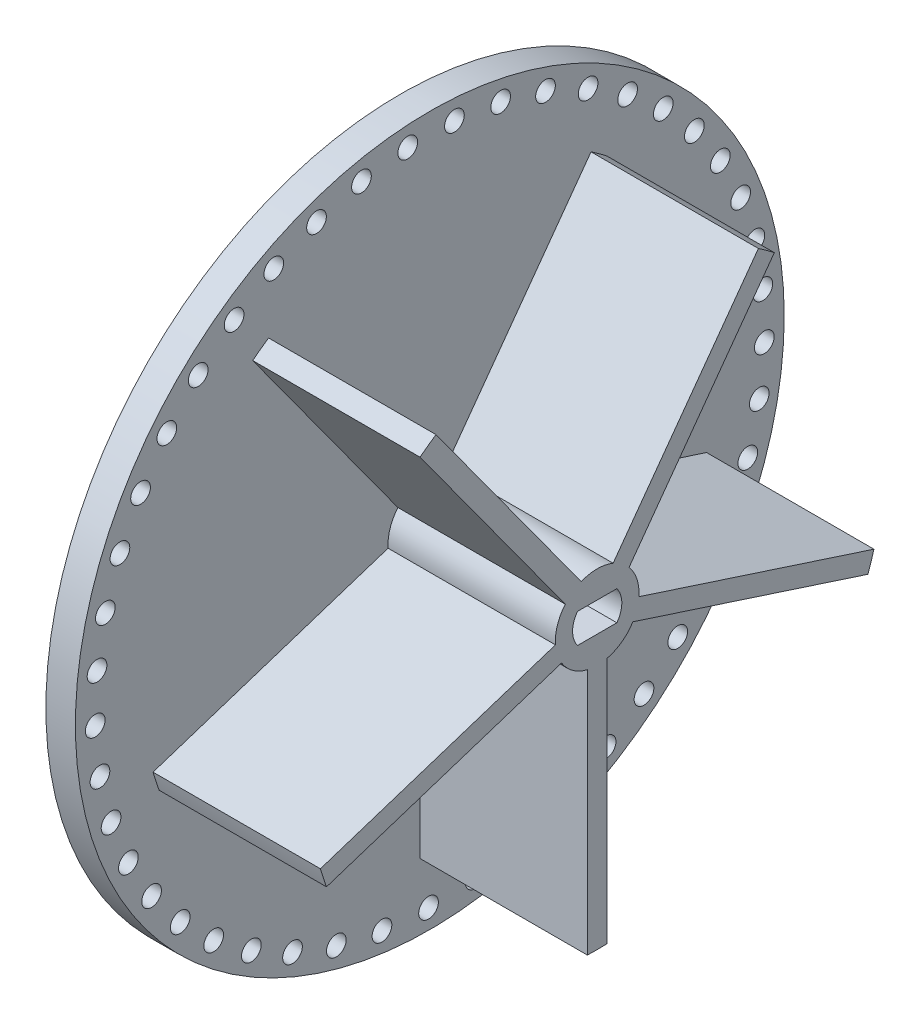
SolidWorks part; units mm, degrees
material "ABS"
ref_plane "Front Plane" through (0, 0, 0) normal (0, 0, 1) x (1, 0, 0)
ref_plane "Top Plane" through (0, 0, 0) normal (0, 1, 0) x (1, 0, 0)
ref_plane "Right Plane" through (0, 0, 0) normal (1, 0, 0) x (0, 0, -1)
sketch "Sketch1" plane through (0, 0, 0) normal (1, 0, 0) x (0, 0, -1)
  line L0 (0, 0) -> (20.089, 27.4305) construction
  line L1 (-2, 1.5) -> (2, 1.5)
  line L3 (-2, -1.5) -> (2, -1.5)
  line L5 (-2, 1.5) -> (2, -1.5) construction
  line L6 (-2, -1.5) -> (2, 1.5) construction
  circle A0 centre (0, 0) radius 30
  arc A1 (-2, 1.5) -> (-2, -1.5) centre (0, 0) ccw
  arc A2 (2, -1.5) -> (2, 1.5) centre (0, 0) ccw
  circle A3 centre (20.089, 27.4305) radius 1
  circle A4 centre (23.7111, 24.3677) radius 1
  circle A5 centre (26.8717, 20.8306) radius 1
  circle A6 centre (29.5092, 16.888) radius 1
  circle A7 centre (31.5724, 12.6168) radius 1
  circle A8 centre (33.0211, 8.1) radius 1
  circle A9 centre (33.827, 3.4255) radius 1
  circle A10 centre (33.9745, -1.3156) radius 1
  circle A11 centre (33.4608, -6.0312) radius 1
  circle A12 centre (32.2958, -10.6293) radius 1
  circle A13 centre (30.5022, -15.0206) radius 1
  circle A14 centre (28.1149, -19.1195) radius 1
  circle A15 centre (25.1803, -22.8463) radius 1
  circle A16 centre (21.7557, -26.1283) radius 1
  circle A17 centre (17.9076, -28.9019) radius 1
  circle A18 centre (13.711, -31.1129) radius 1
  circle A19 centre (9.2475, -32.7183) radius 1
  circle A20 centre (4.604, -33.6868) radius 1
  circle A21 centre (-0.1292, -33.9998) radius 1
  circle A22 centre (-4.8597, -33.6509) radius 1
  circle A23 centre (-9.4957, -32.6471) radius 1
  circle A24 centre (-13.9469, -31.0078) radius 1
  circle A25 centre (-18.1267, -28.765) radius 1
  circle A26 centre (-21.9536, -25.9623) radius 1
  circle A27 centre (-25.3532, -22.6543) radius 1
  circle A28 centre (-28.2593, -18.9054) radius 1
  circle A29 centre (-30.6154, -14.7884) radius 1
  circle A30 centre (-32.3756, -10.3837) radius 1
  circle A31 centre (-33.5056, -5.7768) radius 1
  circle A32 centre (-33.9836, -1.0575) radius 1
  circle A33 centre (-33.8, 3.6824) radius 1
  circle A34 centre (-32.9586, 8.3506) radius 1
  circle A35 centre (-31.4756, 12.8563) radius 1
  circle A36 centre (-29.3801, 17.1117) radius 1
  circle A37 centre (-26.7127, 21.0341) radius 1
  circle A38 centre (-23.5253, 24.5471) radius 1
  circle A39 centre (-19.8801, 27.5823) radius 1
  circle A40 centre (-15.8479, 30.0806) radius 1
  circle A41 centre (-11.5072, 31.9935) radius 1
  circle A42 centre (-6.9426, 33.2836) radius 1
  circle A43 centre (-2.2429, 33.9259) radius 1
  circle A44 centre (2.5005, 33.9079) radius 1
  circle A45 centre (7.1953, 33.2299) radius 1
  circle A46 centre (11.75, 31.9051) radius 1
  circle A47 centre (16.076, 29.9594) radius 1
  circle A48 centre (0, 0) radius 4.25
  circle A49 centre (0, 0) radius 36
  circle A50 centre (0, 0) radius 32
  dimension "D1" = 60
  dimension "D4" = 2
  dimension "D7" = 8.5
  dimension "D8" = 72
  dimension "D2" = 4
  dimension "D3" = 3
  dimension "D5" = 34
  dimension "D9" = 2
  dimension "D6" = 45
extrude "Boss-Extrude1" add sketch "Sketch1" along normal blind 3 contours A0 A48 | A50 A0 | A49 A50 A3 A4 A5 A6 A7 A8 A9 A10 A11 A12 A13 A14 A15 A16 A17 A18 A19 A20 A21 A22 A23 A24 A25 A26 region at (0, 0, 29.1515) region at (0, 0, 34.9818) region at (0, 0, 31.0949)
extrude "Boss-Extrude2" add sketch "Sketch1<3>" along normal blind 20 contours A48 A2 L3 A1 L1 region at (0, 0, 4.1298)
sketch "Sketch1<3>" plane through (0, 0, 0) normal (1, 0, 0) x (0, 0, -1) same geometry as "Sketch1"
extrude "Boss-Extrude3" add sketch "Sketch1<4>" along normal blind 3 contours L3 A2 L1 A1 region at (0, 0, 0)
sketch "Sketch1<4>" plane through (0, 0, 0) normal (1, 0, 0) x (0, 0, -1) same geometry as "Sketch1"
sketch "Sketch2" plane through (3, 0, 0) normal (1, 0, 0) x (0, 0, -1)
  line L1 (-1, -4.1307) -> (-1, -29.2329)
  line L2 (1, -4.1307) -> (1, -29.2329)
  line L3 (-3.6195, -2.2275) -> (-27.4931, -9.9845)
  line L4 (-4.2375, -0.3254) -> (-28.1112, -8.0824)
  line L5 (-3.237, 2.754) -> (-17.9917, 23.0621)
  line L6 (-1.6189, 3.9296) -> (-16.3737, 24.2377)
  line L7 (1.6189, 3.9296) -> (16.3737, 24.2377)
  line L8 (3.237, 2.754) -> (17.9917, 23.0621)
  line L9 (4.2375, -0.3254) -> (28.1112, -8.0824)
  line L10 (3.6195, -2.2275) -> (27.4931, -9.9845)
  circle A0 centre (0, 0) radius 4.25 construction
  arc A1 (-1, -4.1307) -> (1, -4.1307) centre (0, 0) ccw
  circle A4 centre (0, 0) radius 4.25 construction
  arc A5 (-1, -4.1307) -> (1, -4.1307) centre (0, 0) ccw
  arc A6 (-1, -29.2329) -> (1, -29.2329) centre (0, 0) ccw
  circle A7 centre (0, 0) radius 29.25 construction
  circle A8 centre (0, 0) radius 4.25 construction
  arc A9 (-28.1112, -8.0824) -> (-27.4931, -9.9845) centre (0, 0) ccw
  arc A10 (-4.2375, -0.3254) -> (-3.6195, -2.2275) centre (0, 0) ccw
  arc A11 (-16.3737, 24.2377) -> (-17.9917, 23.0621) centre (0, 0) ccw
  arc A12 (-1.6189, 3.9296) -> (-3.237, 2.754) centre (0, 0) ccw
  arc A13 (17.9917, 23.0621) -> (16.3737, 24.2377) centre (0, 0) ccw
  arc A14 (3.237, 2.754) -> (1.6189, 3.9296) centre (0, 0) ccw
  arc A15 (27.4931, -9.9845) -> (28.1112, -8.0824) centre (0, 0) ccw
  arc A16 (3.6195, -2.2275) -> (4.2375, -0.3254) centre (0, 0) ccw
  circle M22 centre (0, 0) radius 4.25
  dimension "D2" = 5
  dimension "D1" = 25
extrude "Boss-Extrude5" add sketch "Sketch2" along normal up to surface (17 mm away) contours L4 A9 L3 M22 | L8 A13 L7 M22 | L10 A15 L9 M22 | L1 A6 L2 M22 | L5 A11 L6 A12 region at (3, -16.7274, 0) region at (3, -5.169, 15.9087) region at (3, -5.169, -15.9087) region at (3, 13.5327, -9.8321) up to face at (20, 0, 0)
sketch "Sketch3" plane through (0, 0, 0) normal (-1, 0, 0) x (0, 0, 1)
  circle A0 centre (0, 0) radius 2.2
  dimension "D1" = 4.4
extrude "Cut-Extrude1" cut sketch "Sketch3" against normal blind 10
